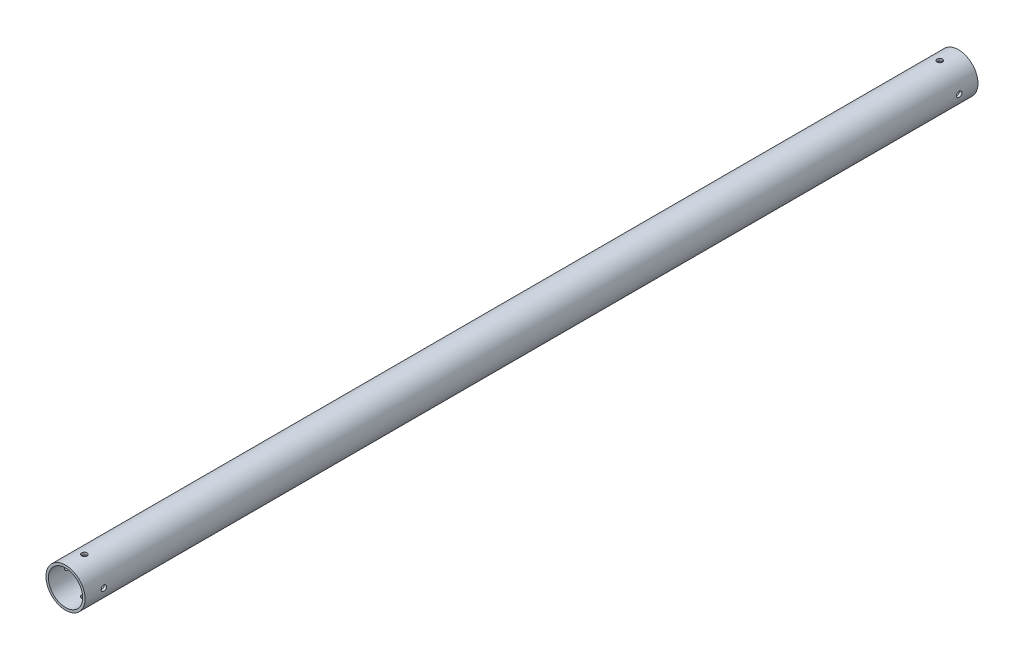
SolidWorks part; units mm, degrees
material "PC High Viscosity"
ref_plane "Front Plane" through (0, 0, 0) normal (0, 0, 1) x (1, 0, 0)
ref_plane "Top Plane" through (0, 0, 0) normal (0, 1, 0) x (1, 0, 0)
ref_plane "Right Plane" through (0, 0, 0) normal (1, 0, 0) x (0, 0, -1)
sketch "Sketch2" plane through (0, 0, 0) normal (0, 0, 1) x (1, 0, 0)
  circle A0 centre (0, 0) radius 11.1125
  circle A1 centre (0, 0) radius 12.7
  dimension "D1" = 25.4
  dimension "D2" = 1.5875
extrude "Boss-Extrude1" add sketch "Sketch2" along normal mid plane 579.1873
sketch "Sketch3" plane through (0, 0, 0) normal (0, 1, 0) x (1, 0, 0)
  line L0 (12.7, 289.5936) -> (-12.7, 289.5936) construction
  line L1 (-55, 0) -> (55, 0) construction
  circle A0 centre (0, 277.4016) radius 1.7526
  circle A1 centre (0, -277.4016) radius 1.7526
  dimension "D1" = 3.5052
  dimension "D2" = 12.192
extrude "Cut-Extrude1" cut sketch "Sketch3" against normal through all both and the other way through all
sketch "Sketch5" plane through (0, 0, 0) normal (1, 0, 0) x (0, 0, -1)
  line L0 (289.5936, -12.7) -> (289.5936, 12.7) construction
  line L1 (0, 55) -> (0, -55) construction
  circle A0 centre (277.4016, 0) radius 1.7526
  circle A1 centre (-277.4016, 0) radius 1.7526
  dimension "D1" = 3.5052
  dimension "D2" = 12.192
extrude "Cut-Extrude2" cut sketch "Sketch5" against normal through all both and the other way through all
